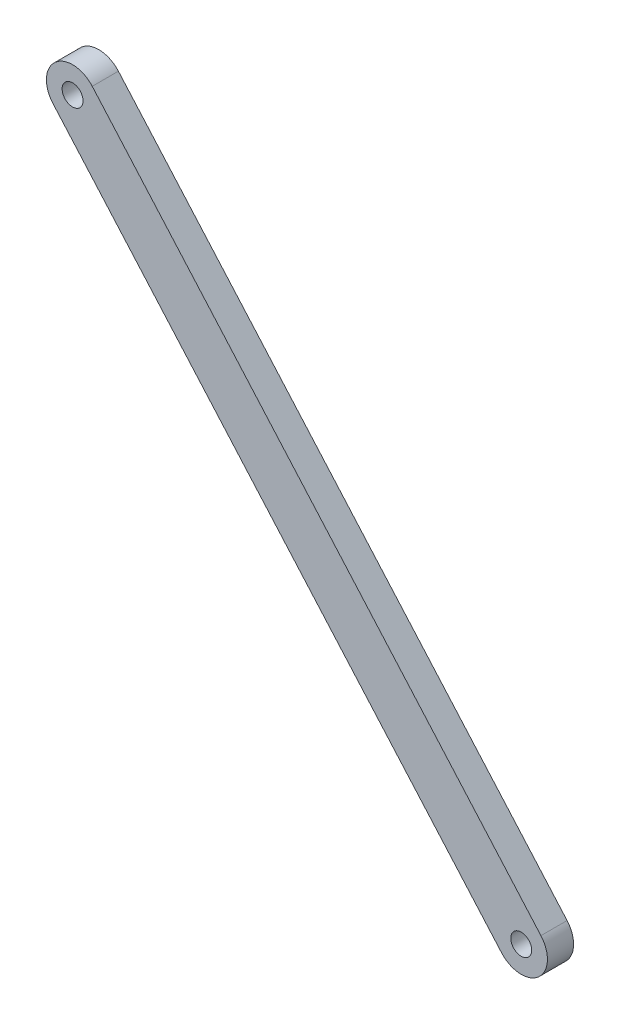
SolidWorks part; units mm, degrees
ref_plane "Front Plane" through (0, 0, 0) normal (0, 0, 1) x (1, 0, 0)
ref_plane "Top Plane" through (0, 0, 0) normal (0, 1, 0) x (1, 0, 0)
ref_plane "Right Plane" through (0, 0, 0) normal (1, 0, 0) x (0, 0, -1)
sketch "Sketch1" plane through (0, 0, 0) normal (0, 0, 1) x (1, 0, 0)
  line L0 (-120.1684, 144.5246) -> (-34.4158, 46.8185)
  line L1 (-41.9316, 40.2221) -> (-127.6843, 137.9282)
  circle A0 centre (-38.1737, 43.5203) radius 2 construction
  circle A1 centre (-38.1737, 43.5203) radius 2
  circle A2 centre (-123.9264, 141.2264) radius 2 construction
  circle A3 centre (-123.9264, 141.2264) radius 2
  arc A4 (-34.4158, 46.8185) -> (-41.9316, 40.2221) centre (-38.1737, 43.5203) cw
  arc A5 (-127.6843, 137.9282) -> (-120.1684, 144.5246) centre (-123.9264, 141.2264) cw
  point P0 (0, 0)
  point P12 (0, 0)
  dimension "D1" = 5
  dimension "D2" = 5
extrude "Boss-Extrude1" add sketch "Sketch1" along normal blind 5 from offset 5
